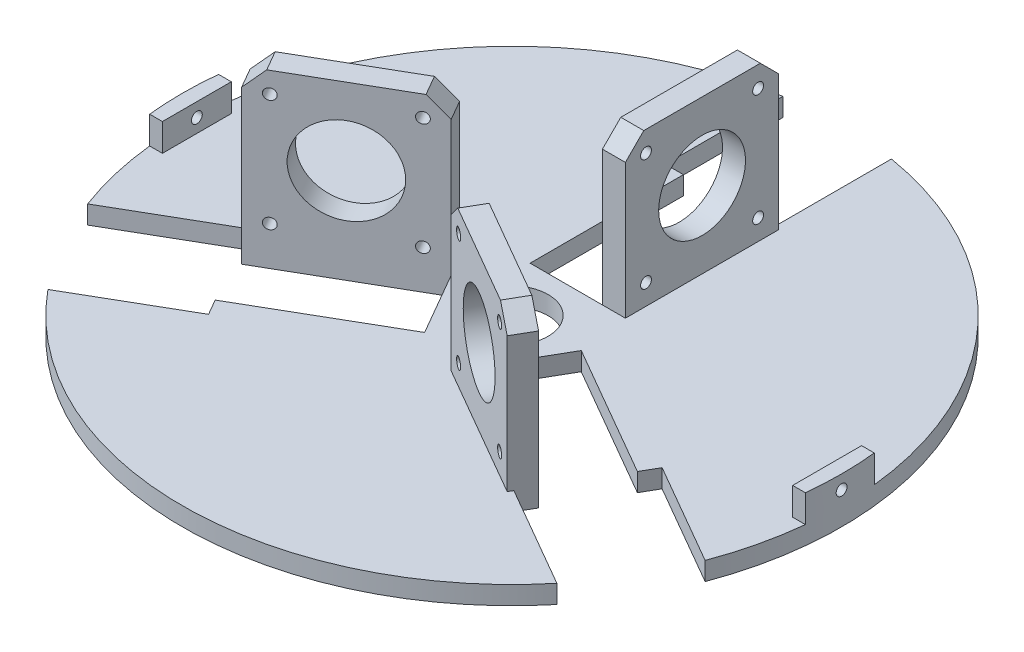
SolidWorks part; units mm, degrees
ref_plane "Front" through (0, 0, 0) normal (0, 0, 1) x (1, 0, 0)
ref_plane "Top" through (0, 0, 0) normal (0, 1, 0) x (1, 0, 0)
ref_plane "Right" through (0, 0, 0) normal (1, 0, 0) x (0, 0, -1)
sketch "Sketch1" plane through (0, 0, 0) normal (0, 1, 0) x (1, 0, 0)
  line L0 (0, 0) -> (0, 15) construction
  line L4 (-10, 115) -> (-10, 15)
  line L5 (-10, 115) -> (10, 115)
  line L6 (-10, 15) -> (10, 15)
  line L7 (10, 115) -> (10, 15)
  line L8 (-10, 115) -> (10, 15) construction
  line L9 (-10, 15) -> (10, 115) construction
  line L10 (94.5929, -66.1603) -> (7.9904, -16.1603)
  line L11 (104.5929, -48.8397) -> (94.5929, -66.1603)
  line L12 (104.5929, -48.8397) -> (17.9904, 1.1603)
  line L13 (17.9904, 1.1603) -> (7.9904, -16.1603)
  line L14 (104.5929, -48.8397) -> (7.9904, -16.1603) construction
  line L15 (17.9904, 1.1603) -> (94.5929, -66.1603) construction
  line L16 (-104.5929, -48.8397) -> (-17.9904, 1.1603)
  line L17 (-94.5929, -66.1603) -> (-104.5929, -48.8397)
  line L18 (-94.5929, -66.1603) -> (-7.9904, -16.1603)
  line L19 (-7.9904, -16.1603) -> (-17.9904, 1.1603)
  line L20 (-94.5929, -66.1603) -> (-17.9904, 1.1603) construction
  line L21 (-7.9904, -16.1603) -> (-104.5929, -48.8397) construction
  line L22 (16.35, 57.3926) -> (16.35, 15)
  line L23 (10, 57.3926) -> (64.35, 57.3926)
  line L24 (10, 57.3926) -> (10, 15)
  line L25 (10, 15) -> (64.35, 15)
  line L26 (64.35, 57.3926) -> (64.35, 15)
  line L27 (44.7034, -37.3566) -> (7.9904, -16.1603)
  line L28 (44.7034, -37.3566) -> (17.5284, -84.425)
  line L29 (17.5284, -84.425) -> (-19.1846, -63.2287)
  line L30 (7.9904, -16.1603) -> (-19.1846, -63.2287)
  line L31 (41.5284, -42.8558) -> (4.8154, -21.6595)
  line L32 (-54.7034, -20.036) -> (-17.9904, 1.1603)
  line L33 (-54.7034, -20.036) -> (-81.8784, 27.0324)
  line L34 (-81.8784, 27.0324) -> (-45.1654, 48.2287)
  line L35 (-17.9904, 1.1603) -> (-45.1654, 48.2287)
  line L36 (-57.8784, -14.5368) -> (-21.1654, 6.6595)
  line L37 (57.2034, -15.7059) -> (107.0929, -44.5096)
  line L38 (-15, 57.3926) -> (15, 57.3926)
  line L39 (-15, 57.3926) -> (-15, 115)
  line L40 (-15, 115) -> (15, 115)
  line L41 (15, 57.3926) -> (15, 115)
  line L42 (-15, 57.3926) -> (15, 115) construction
  line L43 (-15, 115) -> (15, 57.3926) construction
  line L44 (57.2034, -15.7059) -> (42.2034, -41.6867)
  line L45 (42.2034, -41.6867) -> (92.0929, -70.4904)
  line L46 (107.0929, -44.5096) -> (92.0929, -70.4904)
  line L47 (-42.2034, -41.6867) -> (-92.0929, -70.4904)
  line L48 (-42.2034, -41.6867) -> (-57.2034, -15.7059)
  line L49 (-57.2034, -15.7059) -> (-107.0929, -44.5096)
  line L50 (-92.0929, -70.4904) -> (-107.0929, -44.5096)
  line L51 (87.122, 9.525) -> (87.122, -9.525)
  line L52 (-55, 0) -> (55, 0) construction
  line L53 (87.122, 9.525) -> (90.6409, 9.525)
  line L54 (87.122, -9.525) -> (90.6409, -9.525)
  line L55 (0, -55) -> (0, 55) construction
  line L56 (-87.122, -9.525) -> (-90.6409, -9.525)
  line L57 (-87.122, 9.525) -> (-90.6409, 9.525)
  line L58 (-87.122, 9.525) -> (-87.122, -9.525)
  circle A0 centre (0, 0) radius 91.14
  circle A1 centre (0, 0) radius 10
  arc A2 (90.6409, 9.525) -> (90.6409, -9.525) centre (0, 0) cw
  point P2 (0, 15)
  point P4 (0, 65)
  point P20 (0, 0)
  point P29 (0, 86.1963)
  point P39 (0, 0)
  point P54 (0, 0)
  point P55 (87.122, 0)
  dimension "D7" = 182.28
  dimension "D11" = 20
  dimension "D1" = 15
  dimension "D2" = 20
  dimension "D4" = 6.35
  dimension "D5" = 48
  dimension "D6" = 42.3926
  dimension "D9" = 30
  dimension "D10" = 100
  dimension "D13" = 19.05
  dimension "D14" = 87.122
  dimension "D3" = 3
  dimension "D8" = 3
  dimension "D12" = 3
extrude "Base" add sketch "Sketch1" along normal blind 5.08 contours L12 A0 L7 L23 L26 L25 L6 L4 L16 L33 L34 L35 L19 L18 L10 L28 L29 L30 L13 | L31 L28 L10 L30 | L36 L33 L16 L35 | L7 L25 L22 L23 | L54 A0 L53 L51 | L57 A0 L56 L58 | L27 L30 L29 L28 | L32 L35 L34 L33 | L24 L23 L26 L25 region at (-12.562, 0, -36.1963) region at (13.175, 0, -36.1963) region at (-89.0508, 0, 0) region at (89.0508, 0, 0) region at (-37.9344, 0, 6.6883) region at (24.7594, 0, 29.508)
sketch "Sketch2" plane through (-5, 0, 8.6603) normal (0.5, 0, -0.866) x (-0.866, 0, -0.5)
  line L0 (-15, 47.47) -> (-57.3926, 5.08) construction
  line L5 (-57.3926, 5.08) -> (-15, 5.08) construction
  line L6 (-15, 5.08) -> (-57.3926, 5.08)
  line L7 (-57.3926, 47.47) -> (-15, 5.08) construction
  line L10 (-15, 5.08) -> (-15, 42.39)
  line L11 (-20.08, 47.47) -> (-52.3126, 47.47)
  line L12 (-57.3926, 5.08) -> (-57.3926, 42.39)
  line L13 (-15, 42.39) -> (-20.08, 47.47)
  line L14 (-52.3126, 47.47) -> (-57.3926, 42.39)
  circle A5 centre (-36.1963, 26.275) radius 12
  circle A7 centre (-20.7018, 41.7685) radius 1.5
  circle A8 centre (-20.7028, 10.7805) radius 1.5
  circle A9 centre (-51.6908, 10.7815) radius 1.5
  circle A10 centre (-51.6898, 41.7695) radius 1.5
  point P14 (-36.1963, 26.275)
  point P22 (-36.1963, 26.275)
  dimension "D1" = 42.39
  dimension "D3" = 4
  dimension "D4" = 30.988
  dimension "D2" = 3
  dimension "D5" = 24
ref_axis "Axis1" through (0, -2.504, 0) along (0, 1, 0)
extrude "MotorExtrude" add sketch "Sketch2" against normal up to vertex (6.35 mm away) up to point (41.5284, 0, 42.8558)
pattern_circular "CirPattern3" count 3 over 240 about axis through (0, -2.504, 0) along (0, 1, 0) of "MotorExtrude"
extrude "Boss-Extrude1" add sketch "Sketch1<7>" along normal blind 12.7 contours L57 A0 L56 L58 | L51 L54 A2 L53 region at (-89.0508, 0, 0)
sketch "Sketch1<7>" plane through (0, 0, 0) normal (0, 1, 0) x (1, 0, 0) same geometry as "Sketch1"
sketch "Sketch3" plane through (87.122, 0, 0) normal (-1, 0, 0) x (0, 0, 1)
  line L0 (0, -55) -> (0, 55) construction
  line L1 (9.525, 12.7) -> (-9.525, 12.7) construction
  circle A0 centre (0, 8.89) radius 1.5
  dimension "D1" = 3
  dimension "D2" = 3.81
extrude "Cut-Extrude1" cut sketch "Sketch3" against normal through all
mirror "Mirror1" about plane through (0, 0, 0) normal (1, 0, 0) of "Cut-Extrude1"
